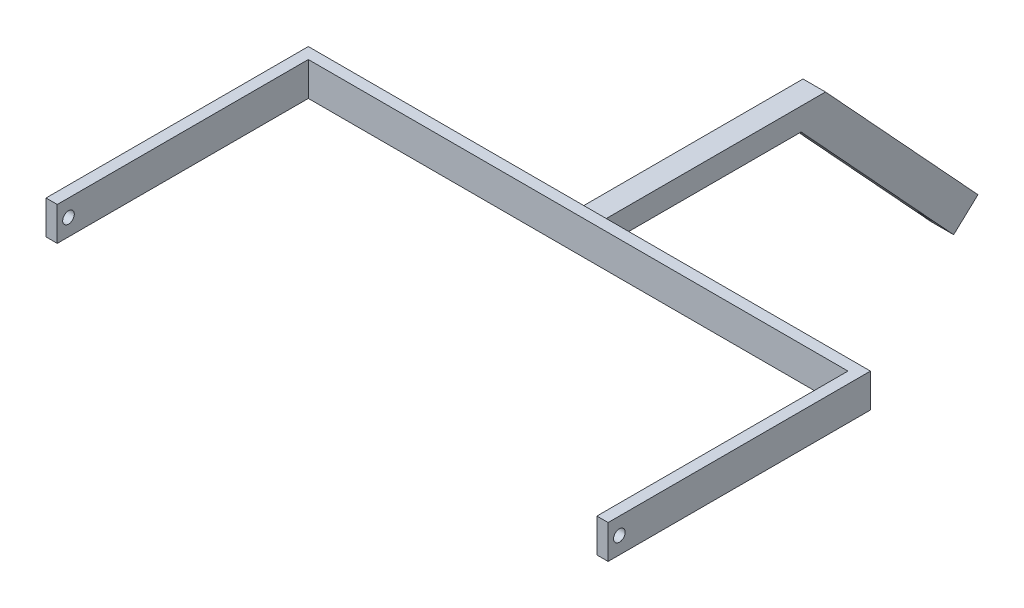
SolidWorks part; units mm, degrees
ref_plane "前视基准面" through (0, 0, 0) normal (0, 0, 1) x (1, 0, 0)
ref_plane "上视基准面" through (0, 0, 0) normal (0, 1, 0) x (1, 0, 0)
ref_plane "右视基准面" through (0, 0, 0) normal (1, 0, 0) x (0, 0, -1)
other "Configuration Table"
sketch "草图1" plane through (0, 0, 0) normal (0, 1, 0) x (1, 0, 0)
  line L0 (-72.7576, -1.4848) -> (-72.7576, -68.4848)
  line L1 (71.2424, -1.4848) -> (-72.7576, -1.4848)
  line L2 (74.2424, -1.4848) -> (74.2424, 1.5152)
  line L3 (74.2424, 1.5152) -> (-75.7576, 1.5152)
  line L4 (-75.7576, -1.4848) -> (-75.7576, 1.5152)
  line L5 (71.2424, -1.4248) -> (-75.7576, 1.5152) construction
  line L6 (74.2424, 1.5152) -> (-72.7576, -1.4848) construction
  line L7 (-75.7576, 1.5152) -> (-72.7576, 1.5152)
  line L8 (-75.7576, 1.5152) -> (-75.7576, -68.4848)
  line L9 (-75.7576, -68.4848) -> (-72.7576, -68.4848)
  line L10 (-72.7576, 1.5152) -> (-72.7576, 1.4552)
  line L11 (74.2424, 1.5152) -> (71.2424, 1.5152)
  line L12 (74.2424, 1.5152) -> (74.2424, -68.4848)
  line L13 (74.2424, -68.4848) -> (71.2424, -68.4848)
  line L14 (71.2424, 1.5152) -> (71.2424, 1.4539)
  line L15 (71.2424, -1.4248) -> (71.2424, -68.4848)
  point P0 (0, 0)
  point P12 (-72.7576, -1.4848)
  point P13 (71.2424, -1.4848)
  dimension "D1" = 150
  dimension "D2" = 3
  dimension "D3" = 3
  dimension "D4" = 70
  dimension "D5" = 70
  dimension "D6" = 3
  dimension "D7" = 67
  dimension "D8" = 67.06
  dimension "D9" = 150
  dimension "D10" = 67
extrude "凸台-拉伸2" add sketch "草图1" along normal blind 6 contours L1 L15 L13 L12 L2 L3 L4 L8 L9 L0 region at (-74.4129, 0, 34.9848)
sketch "草图2" plane through (-72.7576, 0, 0) normal (1, 0, 0) x (0, 0, -1)
  line L0 (-68.4848, 6) -> (-68.4848, 0) construction
  line L1 (-1.4848, 0) -> (-68.4848, 0) construction
  circle A0 centre (-65.4848, 3) radius 1.55
  dimension "D2" = 3.1
  dimension "D1" = 3
  dimension "D3" = 3
extrude "切除-拉伸1" cut sketch "草图2" against normal blind 10
sketch "草图3" plane through (74.2424, 0, 0) normal (1, 0, 0) x (0, 0, -1)
  line L0 (-68.4848, 6) -> (-68.4848, 0) construction
  line L1 (1.5152, 0) -> (-68.4848, 0) construction
  circle A0 centre (-65.4848, 3) radius 1.55
  dimension "D2" = 3.1
  dimension "D1" = 3
  dimension "D3" = 3
extrude "切除-拉伸2" cut sketch "草图3" against normal blind 10 contours A0
sketch "草图5" plane through (0, 0, -1.5152) normal (0, 0, -1) x (-1, 0, 0)
  line L3 (3.7576, 0) -> (-2.2424, 0)
  line L4 (3.7576, 0) -> (3.7576, 6)
  line L5 (3.7576, 6) -> (-2.2424, 6)
  line L6 (-2.2424, 0) -> (-2.2424, 6)
  line L7 (3.7576, 0) -> (-2.2424, 6) construction
  line L8 (3.7576, 6) -> (-2.2424, 0) construction
  line L9 (75.7576, 6) -> (75.7576, 0) construction
  line L12 (-74.2424, 0) -> (75.7576, 0) construction
  point P0 (0.7576, 3)
  dimension "D3" = 6
  dimension "D1" = 75
  dimension "D2" = 3
  dimension "D4" = 6
sketch "草图6" plane through (0, 6, 0) normal (0, 1, 0) x (1, 0, 0)
  line L0 (-75.7576, 1.5152) -> (74.2424, 1.5152)
  line L1 (74.2424, 1.5152) -> (74.2424, -68.4848)
  line L2 (74.2424, -68.4848) -> (71.2424, -68.4848)
  line L3 (71.2424, -68.4848) -> (71.2424, -1.4848)
  line L4 (71.2424, -1.4848) -> (-72.7576, -1.4848)
  line L5 (-72.7576, -1.4848) -> (-72.7576, -68.4848)
  line L6 (-72.7576, -68.4848) -> (-75.7576, -68.4848)
  line L7 (-75.7576, -68.4848) -> (-75.7576, 1.5152)
extrude "凸台-拉伸4" add sketch "草图6" along normal blind 1.5
sketch "草图7" plane through (0, 0, 0) normal (0, -1, 0) x (1, 0, 0)
  line L0 (-75.7576, 68.4848) -> (-75.7576, -1.5152)
  line L1 (-75.7576, -1.5152) -> (74.2424, -1.5152)
  line L2 (74.2424, -1.5152) -> (74.2424, 68.4848)
  line L3 (74.2424, 68.4848) -> (71.2424, 68.4848)
  line L4 (71.2424, 68.4848) -> (71.2424, 1.4848)
  line L5 (71.2424, 1.4848) -> (-72.7576, 1.4848)
  line L6 (-72.7576, 1.4848) -> (-72.7576, 68.4848)
  line L7 (-72.7576, 68.4848) -> (-75.7576, 68.4848)
extrude "凸台-拉伸5" add sketch "草图7" along normal blind 1.5
extrude "凸台-拉伸6" add sketch "草图5" along normal blind 60 contours L5 L6 L3 L4
sketch "草图8" plane through (2.2424, 0, 0) normal (1, 0, 0) x (0, 0, -1)
  line L0 (61.5152, 6) -> (55.0152, 0)
  line L1 (61.5152, 0) -> (1.5152, 0) construction
  line L2 (55.0152, 0) -> (61.5152, 0)
  line L3 (61.5152, 0) -> (61.5152, 6)
  dimension "D1" = 6.5
extrude "切除-拉伸3" cut sketch "草图8" against normal blind 60
sketch "草图9" plane through (0, -27.4197, -25.3105) normal (0, -0.7348, -0.6783) x (1, 0, 0)
  line L0 (-3.7576, -40.4253) -> (-3.7576, -49.2712)
  line L1 (-3.7576, -49.2712) -> (2.2424, -49.2712)
  line L2 (2.2424, -49.2712) -> (2.2424, -40.4253)
  line L3 (2.2424, -40.4253) -> (-3.7576, -40.4253)
extrude "凸台-拉伸7" add sketch "草图9" along normal blind 60
sketch "草图10" plane through (0, -71.5079, -66.0073) normal (0, -0.7348, -0.6783) x (1, 0, 0)
  line L0 (-3.7576, -40.4253) -> (2.2424, -49.2712) construction
  line L1 (-3.7576, -49.2712) -> (2.2424, -40.4253) construction
  line L3 (1.7424, -47.8483) -> (-3.2576, -47.8483)
  line L4 (1.7424, -47.8483) -> (1.7424, -41.8483)
  line L5 (1.7424, -41.8483) -> (-3.2576, -41.8483)
  line L6 (-3.2576, -47.8483) -> (-3.2576, -41.8483)
  line L7 (1.7424, -47.8483) -> (-3.2576, -41.8483) construction
  line L8 (1.7424, -41.8483) -> (-3.2576, -47.8483) construction
  point P8 (-0.7576, -44.8483)
  point P9 (-0.7576, -44.8483)
  dimension "D1" = 6
  dimension "D2" = 5
sketch "草图11" plane through (0, 33.4197, -36.2047) normal (0, 0.6783, -0.7348) x (-1, 0, 0)
  line L0 (-2.2424, -97.3157) -> (-2.2424, -37.3157) construction
  line L1 (3.7576, -97.3157) -> (-2.2424, -97.3157)
  line L2 (3.7576, -97.3157) -> (3.7576, -87.3157)
  line L3 (3.7576, -87.3157) -> (-2.2424, -87.3157)
  line L4 (-2.2424, -97.3157) -> (-2.2424, -87.3157)
  circle A0 centre (0.7576, -90.3157) radius 1.55
  dimension "D4" = 3.1
  dimension "D1" = 10
  dimension "D2" = 3
  dimension "D3" = 3
extrude "切除-拉伸5" cut sketch "草图11" against normal blind 10 contours A0
extrude "切除-拉伸6" cut sketch "草图10" against normal blind 10
